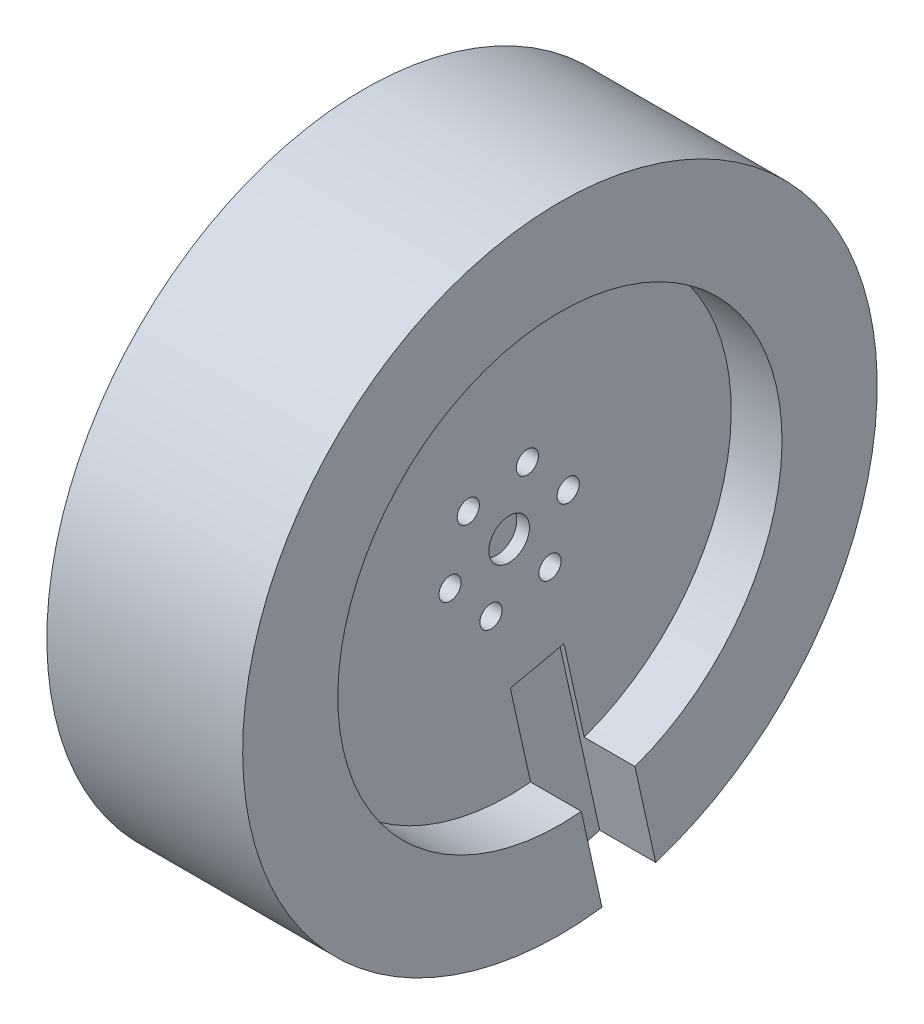
SolidWorks part; units mm, degrees
ref_plane "Front Plane" through (0, 0, 0) normal (0, 0, 1) x (1, 0, 0)
ref_plane "Top Plane" through (0, 0, 0) normal (0, 1, 0) x (1, 0, 0)
ref_plane "Right Plane" through (0, 0, 0) normal (1, 0, 0) x (0, 0, -1)
sketch "Sketch1" plane through (0, 0, 0) normal (1, 0, 0) x (0, 0, -1)
  circle A0 centre (0, 0) radius 50
extrude "Boss-Extrude1" add sketch "Sketch1" along normal blind 30.86
ref_axis "WheelAxis" through (0, 0, 0) along (1, 0, 0)
ref_point "Point1"
ref_point "Point2"
sketch "Sketch2" plane through (30.86, 0, 0) normal (1, 0, 0) x (0, 0, -1)
  circle A0 centre (0, 0) radius 35
extrude "Cut-Extrude1" cut sketch "Sketch2" against normal blind 8
sketch "Sketch3" plane through (0, 0, 0) normal (-1, 0, 0) x (0, 0, 1)
  circle A0 centre (0, 0) radius 29.8357
sketch "Sketch5" plane through (0, 0, 0) normal (-1, 0, 0) x (0, 0, 1)
  line L1 (-2.8683, 9.0881) -> (-9.3047, 2.0601) construction
  line L2 (-9.3047, 2.0601) -> (-6.4364, -7.0281) construction
  line L3 (-6.4364, -7.0281) -> (2.8683, -9.0881) construction
  line L4 (2.8683, -9.0881) -> (9.3047, -2.0601) construction
  line L5 (9.3047, -2.0601) -> (6.4364, 7.0281) construction
  line L6 (6.4364, 7.0281) -> (-2.8683, 9.0881) construction
  circle A0 centre (0, 0) radius 9.53 construction
  circle A1 centre (0, 0) radius 8.2532 construction
  circle A2 centre (2.8683, -9.0881) radius 1.75
  circle A3 centre (-6.4364, -7.0281) radius 1.75
  circle A4 centre (-9.3047, 2.0601) radius 1.75
  circle A5 centre (-2.8683, 9.0881) radius 1.75
  circle A6 centre (6.4364, 7.0281) radius 1.75
  circle A7 centre (9.3047, -2.0601) radius 1.75
ref_axis "ReferenceAxisForOrientation" through (0, -2.0601, 9.3047) along (0, 0.2162, -0.9764)
ref_plane "Plane1" through (0, 0, 0) normal (0, 0.9764, 0.2162) x (1, 0, 0)
sketch "Sketch10" plane through (0, 0, 0) normal (0, 0.9764, 0.2162) x (1, 0, 0)
  line L1 (22.0394, 4.422) -> (32.0581, 4.422)
  line L2 (22.0394, 4.422) -> (22.0394, -4.2399)
  line L3 (22.0394, -4.2399) -> (32.0581, -4.2399)
  line L4 (32.0581, 4.422) -> (32.0581, -4.2399)
extrude "Cut-Extrude4" cut sketch "Sketch10" against normal blind 60 from offset 20 offset against normal yes
ref_point "Point5"
sketch "Sketch12" plane through (22.86, 0, 0) normal (1, 0, 0) x (0, 0, -1)
  circle A0 centre (0, 0) radius 3.2
extrude "Cut-Extrude5" cut sketch "Sketch12" against normal blind 2
extrude "Cut-Extrude3" cut sketch "Sketch5" against normal blind 30
sketch "Sketch8" plane through (0, 0, 0) normal (-1, 0, 0) x (0, 0, 1)
  circle A0 centre (-2.8683, 9.0881) radius 4
  circle A1 centre (6.4364, 7.0281) radius 4
  circle A2 centre (9.3047, -2.0601) radius 4
  circle A3 centre (2.8683, -9.0881) radius 4
  circle A4 centre (-6.4364, -7.0281) radius 4
  circle A5 centre (-9.3047, 2.0601) radius 4
extrude "Cut-Extrude6" cut sketch "Sketch8" against normal blind 10
